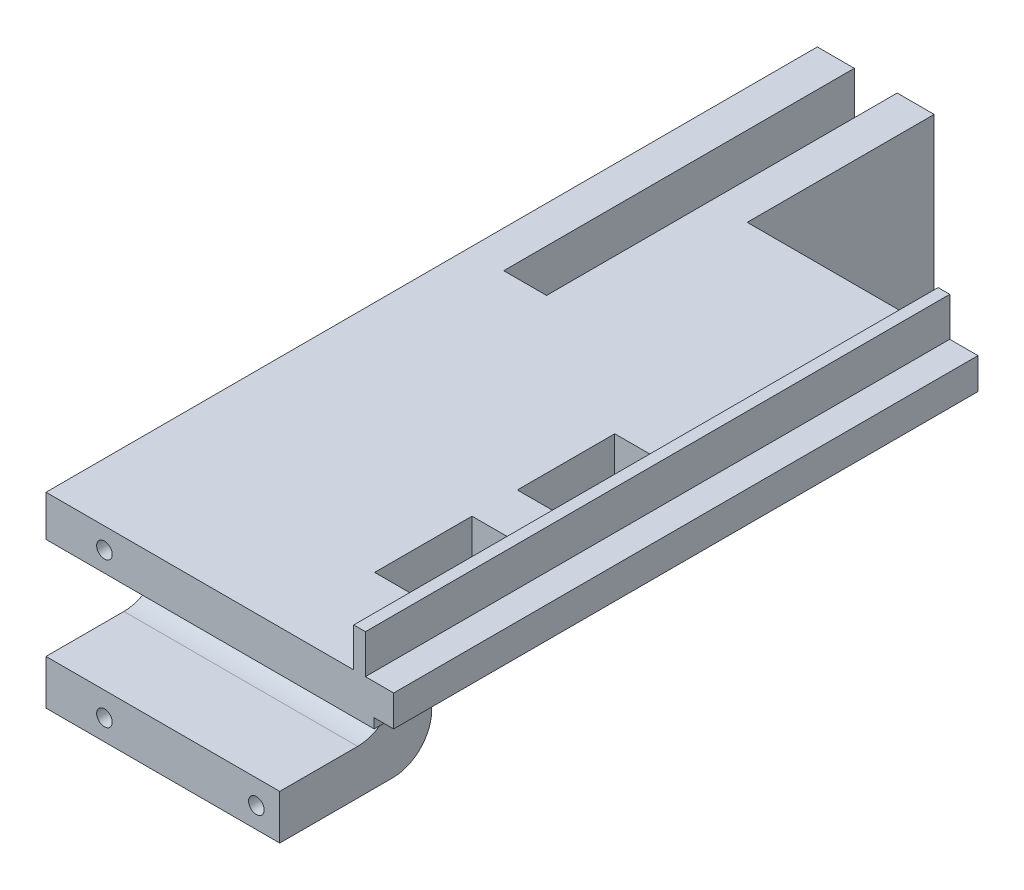
SolidWorks part; units mm, degrees
ref_plane "Alzado" through (0, 0, 0) normal (0, 0, 1) x (1, 0, 0)
ref_plane "Planta" through (0, 0, 0) normal (0, 1, 0) x (1, 0, 0)
ref_plane "Vista lateral" through (0, 0, 0) normal (1, 0, 0) x (0, 0, -1)
sketch "Croquis1" plane through (0, 0, 0) normal (0, 0, 1) x (1, 0, 0)
  line L1 (-66.2162, 31.0113) -> (-6.2162, 31.0113)
  line L2 (-66.2162, 31.0113) -> (-66.2162, -16.9887)
  line L3 (-66.2162, -16.9887) -> (-6.2162, -16.9887)
  line L4 (-6.2162, 31.0113) -> (-6.2162, -16.9887)
  dimension "D1" = 48
  dimension "D2" = 60
extrude "Saliente-Extruir1" add sketch "Croquis1" along normal blind 6
sketch "Croquis4" plane through (0, 0, 6) normal (0, 0, 1) x (1, 0, 0)
  line L0 (-66.2162, 31.0113) -> (-66.2162, 19.5113)
  line L1 (-66.2162, 31.0113) -> (-66.2162, -16.9887) construction
  line L3 (-66.2162, -5.4887) -> (-66.2162, -16.9887)
  line L4 (-66.2162, 31.0113) -> (-6.2162, 31.0113)
  line L6 (-6.2162, 31.0113) -> (-6.2162, 19.5113)
  line L7 (-6.2162, -16.9887) -> (-6.2162, 31.0113) construction
  line L8 (-6.2162, 19.5113) -> (-66.2162, 19.5113)
  line L9 (-66.2162, -5.4887) -> (-6.2162, -5.4887)
  line L10 (-6.2162, -5.4887) -> (-6.2162, -16.9887)
  line L11 (-6.2162, -16.9887) -> (-66.2162, -16.9887)
  dimension "D1" = 25
extrude "Saliente-Extruir3" add sketch "Croquis4" along normal blind 30
sketch "Croquis3" plane through (0, 0, 6) normal (0, 0, 1) x (1, 0, 0)
  circle A0 centre (-51.2162, 25.6613) radius 2.125
  circle A1 centre (-12.2162, 25.6613) radius 2.125
  circle A2 centre (-12.2162, -11.6387) radius 2.125
  circle A3 centre (-51.2162, -11.6387) radius 2.125
  dimension "D7" = 4.25
  dimension "D9" = 4.25
  dimension "D10" = 4.25
  dimension "D2" = 4.25
  dimension "D3" = 37.3
  dimension "D4" = 39
sketch "Croquis5" plane through (0, 0, 36) normal (0, 0, 1) x (1, 0, 0)
  circle A0 centre (-51.2162, 25.6613) radius 2
  circle A1 centre (-12.2162, 25.6613) radius 2
  circle A2 centre (-12.2162, -11.6387) radius 2
  circle A3 centre (-51.2162, -11.6387) radius 2
  dimension "D1" = 4
  dimension "D2" = 4
  dimension "D3" = 4
  dimension "D4" = 4
extrude "Cortar-Extruir3" cut sketch "Croquis5" against normal blind 16
sketch "Croquis6" plane through (0, 0, 0) normal (0, 0, -1) x (-1, 0, 0)
  line L0 (66.2162, -16.9887) -> (6.2162, -16.9887) construction
  line L1 (66.2162, 31.0113) -> (36.2162, 31.0113)
  line L2 (66.2162, 31.0113) -> (66.2162, -16.9887)
  line L3 (66.2162, -16.9887) -> (36.2162, -16.9887)
  line L4 (36.2162, 31.0113) -> (36.2162, -16.9887)
  dimension "D1" = 30
extrude "Saliente-Extruir4" add sketch "Croquis6" along normal blind 162
sketch "Croquis7" plane through (0, 0, -162) normal (0, 0, -1) x (-1, 0, 0)
  circle A0 centre (51.2162, 7.0113) radius 2
  dimension "D1" = 4
extrude "Cortar-Extruir4" cut sketch "Croquis7" against normal blind 16
sketch "Croquis8" plane through (0, 0, -162) normal (0, 0, -1) x (-1, 0, 0)
  line L0 (41.2162, 12.0113) -> (41.2162, 9.5131)
  line L10 (36.2162, 12.0113) -> (41.2162, 12.0113)
  line L11 (36.2162, 12.0113) -> (36.2162, 2.0113)
  line L12 (36.2162, 2.0113) -> (41.2162, 2.0113)
  line L21 (41.2162, 9.5131) -> (44.2162, 9.5131)
  line L23 (41.2162, 4.5131) -> (44.2162, 4.5131)
  line L24 (44.2162, 9.5131) -> (44.2162, 4.5131)
  line L25 (41.2162, 2.0113) -> (41.2162, 4.5131)
  dimension "D1" = 5
  dimension "D2" = 3
  dimension "D3" = 5
sketch "Croquis11" plane through (-36.2162, 0, 0) normal (1, 0, 0) x (0, 0, -1)
  line L1 (-36, 19.5113) -> (-36, 31.0113) construction
  line L4 (-36, 19.5113) -> (-36, 31.0113)
  line L6 (-36, 19.5113) -> (114, 19.5113)
  line L7 (114, 19.5113) -> (114, 31.0113)
  line L8 (162, 31.0113) -> (0, 31.0113) construction
  line L9 (162, 31.0113) -> (0, 31.0113) construction
  line L10 (-36, 31.0113) -> (114, 31.0113)
  dimension "D1" = 150
extrude "Saliente-Extruir6" add sketch "Croquis11" along normal blind 59.25
sketch "Croquis12" plane through (0, 31.0113, 0) normal (0, 1, 0) x (1, 0, 0)
  line L0 (23.0338, -36) -> (-66.2162, -36) construction
  line L1 (15.7838, -36) -> (12.7838, -36)
  line L2 (-66.2162, -36) -> (-66.2162, 162) construction
  line L3 (-66.2162, -36) -> (-66.2162, 162) construction
  line L4 (15.7838, -36) -> (15.7838, 114)
  line L5 (15.7838, 114) -> (12.7838, 114)
  line L6 (23.0338, 114) -> (-36.2162, 114) construction
  line L7 (12.7838, 114) -> (12.7838, -36)
  dimension "D1" = 82
  dimension "D2" = 150
  dimension "D3" = 3
extrude "Saliente-Extruir7" add sketch "Croquis12" along normal blind 10
sketch "Croquis14" plane through (0, 0, -114) normal (0, 0, -1) x (-1, 0, 0)
  line L0 (-23.0338, 23.0113) -> (-18.0338, 23.0113)
  line L1 (-18.0338, 23.0113) -> (-18.0338, 19.5113)
  line L2 (-23.0338, 23.0113) -> (-23.0338, 19.5113)
  line L3 (-23.0338, 19.5113) -> (-18.0338, 19.5113)
  line L4 (36.2162, 19.5113) -> (36.2162, 31.0113)
  line L5 (36.2162, 31.0113) -> (-12.7838, 31.0113)
  line L6 (-23.0338, 31.0113) -> (-23.0338, 19.5113)
  line L7 (-23.0338, 19.5113) -> (36.2162, 19.5113)
  line L8 (36.2162, 19.5113) -> (36.2162, 31.0113) construction
  line L9 (36.2162, 31.0113) -> (-12.7838, 31.0113) construction
  line L10 (-23.0338, 31.0113) -> (-23.0338, 19.5113) construction
  line L11 (-23.0338, 19.5113) -> (36.2162, 19.5113) construction
  line L20 (-12.7838, 31.0113) -> (-12.7838, 41.0113)
  line L22 (-12.7838, 41.0113) -> (-15.7838, 41.0113)
  line L24 (-15.7838, 41.0113) -> (-15.7838, 31.0113)
  line L26 (-15.7838, 31.0113) -> (-23.0338, 31.0113)
  line L27 (-15.7838, 31.0113) -> (-23.0338, 31.0113) construction
  dimension "D2" = 5
  dimension "D3" = 8
  dimension "D1" = 0
extrude "Cortar-Extruir6" cut sketch "Croquis14" against normal through all both and the other way through all
sketch "Croquis15" plane through (0, 0, -162) normal (0, 0, -1) x (-1, 0, 0)
  line L0 (51.2162, 45.0729) -> (51.2162, 16.9496) construction
  line L1 (56.7162, 20.0113) -> (45.7162, 20.0113)
  line L2 (45.7162, 20.0113) -> (45.7162, 31.0113)
  line L3 (56.7162, 20.0113) -> (56.7162, 31.0113)
  line L4 (66.2162, -16.9887) -> (66.2162, 31.0113)
  line L5 (66.2162, 31.0113) -> (36.2162, 31.0113)
  line L6 (36.2162, 31.0113) -> (36.2162, -16.9887)
  line L7 (36.2162, -16.9887) -> (66.2162, -16.9887)
  line L8 (66.2162, -16.9887) -> (66.2162, 31.0113) construction
  line L9 (66.2162, 31.0113) -> (36.2162, 31.0113) construction
  line L10 (56.7162, 31.0113) -> (45.7162, 31.0113)
  point P6 (51.2162, 31.0113)
  point P10 (51.2162, 20.0113)
  dimension "D2" = 11
  dimension "D3" = 11
  dimension "D1" = 0
extrude "Cortar-Extruir7" cut sketch "Croquis15" against normal blind 90 and the other way through all
sketch "Croquis16" plane through (-66.2162, 0, 0) normal (-1, 0, 0) x (0, 0, 1)
  line L0 (6, 19.5113) -> (6, 20.5113)
  line L1 (6, 20.5113) -> (36, 20.5113)
  line L2 (36, 31.0113) -> (36, 19.5113) construction
  line L3 (6, 19.5113) -> (36, 19.5113)
  line L4 (36, 19.5113) -> (36, 20.5113)
  dimension "D1" = 1
extrude "Cortar-Extruir10" cut sketch "Croquis16" against normal through all contours L1 L4 L3 L0
fillet "Redondeo1" radius 10 2 edges at (-36.2162, -5.4887, 6) (-24.0912, 20.5113, 6)
sketch "Croquis20" plane through (0, 0, 0) normal (0, 0, -1) x (-1, 0, 0)
  line L1 (6.2162, 19.5113) -> (36.2162, 19.5113)
  line L2 (6.2162, 19.5113) -> (6.2162, -16.9887)
  line L3 (6.2162, -16.9887) -> (36.2162, -16.9887)
  line L4 (36.2162, 19.5113) -> (36.2162, -16.9887)
extrude "Saliente-Extruir8" add sketch "Croquis20" along normal blind 50
sketch "Croquis21" plane through (0, 19.5113, 0) normal (0, -1, 0) x (1, 0, 0)
  line L1 (5.7838, 11.6411) -> (-6.2162, 11.6411)
  line L2 (5.7838, 11.6411) -> (5.7838, -13.3589)
  line L3 (5.7838, -13.3589) -> (-6.2162, -13.3589)
  line L4 (-6.2162, 11.6411) -> (-6.2162, -13.3589)
  line L5 (18.0338, 11.6411) -> (-6.2162, 11.6411) construction
  line L6 (-6.2162, 36) -> (-6.2162, -50) construction
  line L8 (-6.2162, -50) -> (5.7838, -50)
  line L9 (-6.2162, -50) -> (-6.2162, -25)
  line L10 (-6.2162, -25) -> (5.7838, -25)
  line L11 (5.7838, -50) -> (5.7838, -25)
  dimension "D1" = 12
  dimension "D2" = 25
  dimension "D3" = 25
extrude "Cortar-Extruir11" cut sketch "Croquis21" against normal blind 40
sketch "Croquis22" plane through (0, 0, -50) normal (0, 0, -1) x (-1, 0, 0)
  line L1 (36.2162, 19.5113) -> (6.2162, 19.5113)
  line L2 (36.2162, 19.5113) -> (36.2162, -16.9887)
  line L3 (36.2162, -16.9887) -> (6.2162, -16.9887)
  line L4 (6.2162, 19.5113) -> (6.2162, -16.9887)
extrude "Cortar-Extruir13" cut sketch "Croquis22" against normal blind 47
fillet "Redondeo3" radius 10 1 edges at (-21.2162, -16.9887, -3)
sketch "Croquis23" plane through (0, -16.9887, 0) normal (0, -1, 0) x (1, 0, 0)
  line L0 (-58.7162, -164) -> (-43.7162, -164)
  line L1 (-36.2162, -162) -> (-36.2162, 7) construction
  line L2 (-66.2162, 36) -> (-6.2162, 36) construction
  line L4 (-58.7162, -164) -> (-58.7162, -14)
  line L5 (-43.7162, -164) -> (-43.7162, -14)
  line L6 (-58.7162, -14) -> (-43.7162, -14)
  line L7 (-58.7162, -164) -> (-43.7162, -14) construction
  line L8 (-43.7162, -164) -> (-58.7162, -14) construction
  dimension "D1" = 7.5
  dimension "150" = 150
  dimension "D3" = 50
extrude "Cortar-Extruir14" cut sketch "Croquis23" against normal blind 10
